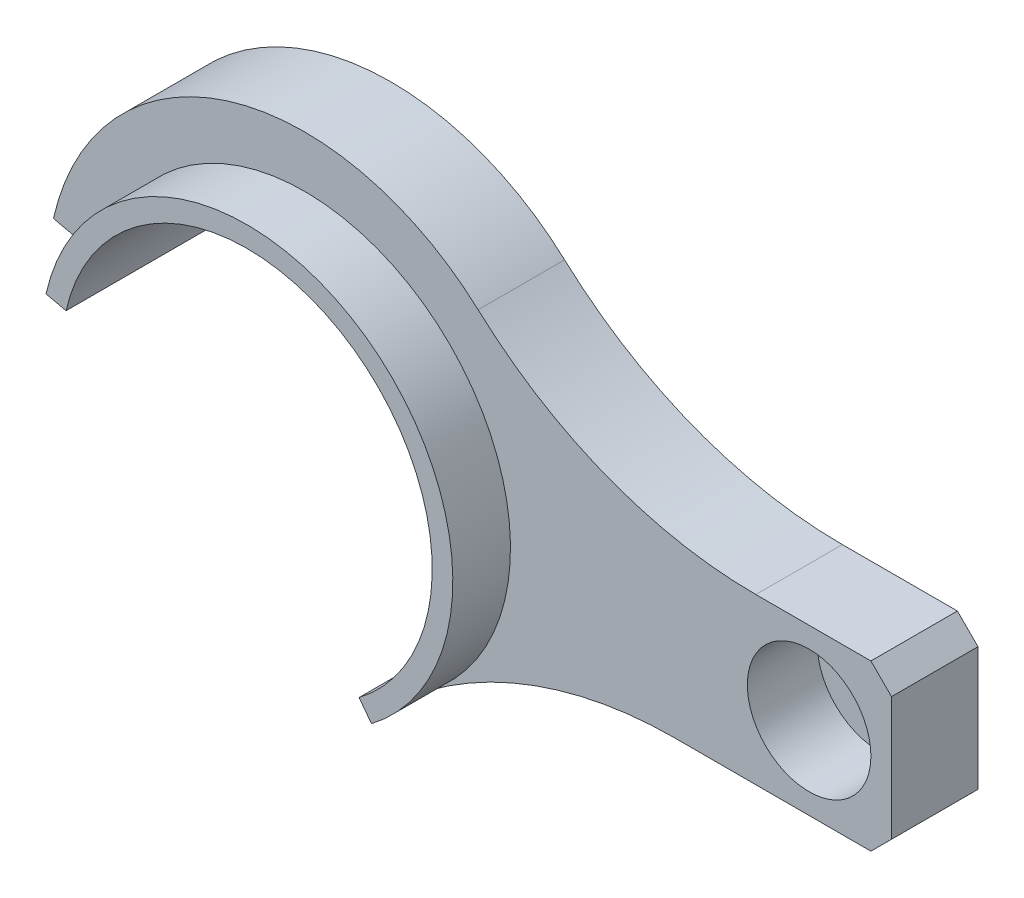
SolidWorks part; units mm, degrees
ref_plane "前视基准面" through (0, 0, 0) normal (0, 0, 1) x (1, 0, 0)
ref_plane "上视基准面" through (0, 0, 0) normal (0, 1, 0) x (1, 0, 0)
ref_plane "右视基准面" through (0, 0, 0) normal (1, 0, 0) x (0, 0, -1)
sketch "草图1" plane through (0, 0, 0) normal (0, 0, 1) x (1, 0, 0)
  line L1 (9.1652, 4) -> (28.5, 4)
  line L2 (9.1652, 4) -> (9.1652, -4) construction
  line L3 (9.1652, -4) -> (28.5, -4)
  line L4 (28.5, 4) -> (28.5, -4)
  arc A0 (9.1652, 4) -> (9.1652, -4) centre (0, 0) ccw
  circle A1 centre (0, 0) radius 9
  arc A2 (9.1652, -4) -> (9.1652, 4) centre (0, 0) ccw construction
  dimension "D1" = 18
  dimension "D2" = 20
  dimension "D3" = 8
  dimension "D4" = 28.5
extrude "凸台-拉伸1" add sketch "草图1" along normal mid plane 4.2
sketch "草图6" plane through (0, 0, -2.1) normal (0, 0, -1) x (-1, 0, 0)
  line L0 (-12.5, 0) -> (-10, 0)
  line L1 (12.5, 0) -> (10, 0)
  arc A0 (-12.5, 0) -> (12.5, 0) centre (0, 0) cw
  arc A1 (-9.1652, -4) -> (-9.1652, 4) centre (0, 0) ccw construction
  arc A2 (10, 0) -> (-10, 0) centre (0, 0) ccw
  dimension "D1" = 2.5
extrude "凸台-拉伸3" add sketch "草图6" against normal up to surface (4.2 mm away) contours A0 L1 A2 L0 up to face at (14.0413, 0, 2.1)
fillet "圆角1" radius 20 2 edges at (9.1652, -4, 0) (11.8427, 4, 0)
sketch "草图2" plane through (0, 0, 2.1) normal (0, 0, 1) x (1, 0, 0)
  line L0 (0, 0) -> (24.5, 0)
  dimension "D1" = 24.5
hole_wizard "打孔尺寸(%根据)内六角圆柱头螺钉的类型3" positions "3D草图1" profile "草图3" counterbore size "M3" standard "GB" end condition up to next
sketch3d "3D草图1"
  point P0 (24.5, 0, 2.1)
sketch "草图3" plane through (24.5, 0, 2.1) normal (1, 0, 0) x (0, -1, 0)
  line L0 (0, 0) -> (0, 4.2)
  line L1 (0, 4.2) -> (1.7, 4.2)
  line L3 (1.7, 4.2) -> (1.7, 3.4)
  line L4 (1.7, 3.4) -> (3, 3.4)
  line L5 (3, 3.4) -> (3, 0)
  line L7 (3, 0) -> (0, 0)
  line L11 (0, -6.35) -> (0, 107.95) construction
  dimension "通孔孔直径" = 3.4
  dimension "通孔孔深度" = 4.2
  dimension "柱形沉头孔直径" = 6
  dimension "柱形沉头孔深度" = 3.4
sketch "草图4" plane through (0, 0, 2.1) normal (0, 0, 1) x (1, 0, 0)
  circle A0 centre (0, 0) radius 9 construction
  circle A1 centre (0, 0) radius 9
  circle A2 centre (0, 0) radius 10
  arc A3 (9.1652, 4) -> (9.1652, -4) centre (0, 0) ccw construction
extrude "凸台-拉伸2" add sketch "草图4" along normal blind 2.8
chamfer "倒角1" distance 1 angle 45 2 edges at (28.5, -4, 0) (28.5, 4, 0)
sketch "草图5" plane through (0, 0, -2.1) normal (0, 0, -1) x (-1, 0, 0)
  line L0 (0, 0) -> (-14.6417, -19.2591)
  line L1 (-14.6417, -19.2591) -> (25.3583, -19.2591)
  line L2 (25.3583, -19.2591) -> (25.3583, 5.7409)
  line L3 (25.3583, 5.7409) -> (0, 0)
  dimension "D1" = 140
  dimension "D2" = 25
  dimension "D3" = 40
  dimension "D4" = 26
extrude "切除-拉伸2" cut sketch "草图5" against normal through all contours L2 L3 L0 L1
